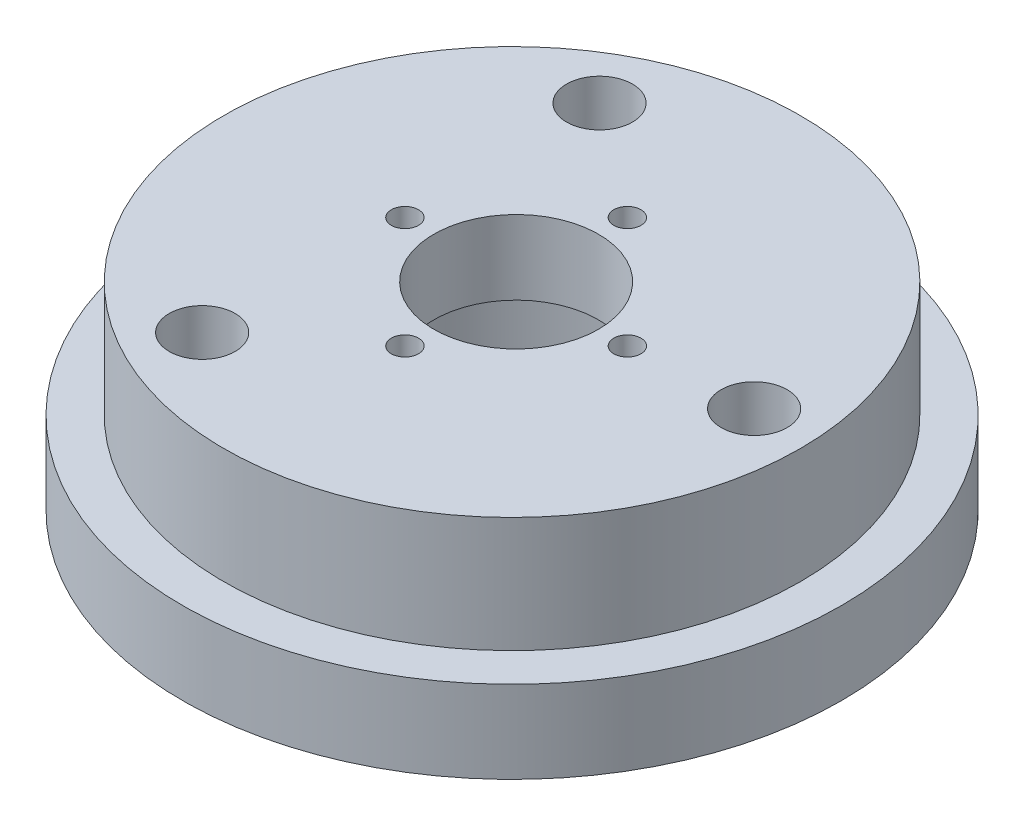
SolidWorks part; units mm, degrees
ref_plane "Front Plane" through (0, 0, 0) normal (0, 0, 1) x (1, 0, 0)
ref_plane "Top Plane" through (0, 0, 0) normal (0, 1, 0) x (1, 0, 0)
ref_plane "Right Plane" through (0, 0, 0) normal (1, 0, 0) x (0, 0, -1)
sketch "Sketch1" plane through (0, 0, 0) normal (0, 0, 1) x (1, 0, 0)
  line L5 (0, 12) -> (0, 0) construction
  line L7 (0, -1000) -> (0, 49000) construction
  line L8 (-40, 10) -> (-35, 10)
  line L9 (-35, 10) -> (-35, 24)
  line L10 (-40, 0) -> (-40, 10)
  line L11 (0, 0) -> (-40, 0)
  line L12 (-35, 24) -> (0, 24)
  line L13 (0, 0) -> (0, 24)
  dimension "D1" = 24
  dimension "D2" = 10
  dimension "D3" = 40
  dimension "D4" = 35
revolve "Revolve1" add sketch "Sketch1" angle 360 about L7
sketch "Sketch2" plane through (0, 0, 0) normal (0, -1, 0) x (1, 0, 0)
  line L0 (-999.7797, -0.2754) -> (49000.2203, -0.2754) construction
  line L1 (0.2203, -1000.2754) -> (0.2203, 48999.7246) construction
  line L2 (0.2203, -2000.2754) -> (0.2203, 97999.7246) construction
  line L3 (-1999.7797, -0.2754) -> (98000.2203, -0.2754) construction
  circle A0 centre (0.2203, -0.2754) radius 10
  circle A1 centre (-13.2797, -0.2754) radius 1.65
  circle A2 centre (13.7203, -0.2754) radius 1.65
  circle A3 centre (0.2203, -0.2754) radius 20
  circle A4 centre (0.2203, 13.2246) radius 1.65
  circle A5 centre (0.2203, -13.7754) radius 1.65
  dimension "D1" = 20
extrude "Cut-Extrude2" cut sketch "Sketch2" against normal through all both and the other way through all contours A0 | A2 | A5 | A1 | A4 region at (0.2203, 0, -0.2754) region at (-13.2797, 0, -0.2754) region at (13.7203, 0, -0.2754) region at (0.2203, 0, 13.2246) region at (0.2203, 0, -13.7754)
extrude "Cut-Extrude3" cut sketch "Sketch2<5>" against normal blind 15 contours A3 A5 A2 A0 A1 A4 region at (-19.214, 0, -0.2754)
sketch "Sketch2<5>" plane through (0, 0, 0) normal (0, -1, 0) x (1, 0, 0) same geometry as "Sketch2"
sketch "Sketch3" plane through (0, 24, 0) normal (0, 1, 0) x (1, 0, 0)
  line L0 (-51.5052, 0) -> (51.5052, 0) construction
  line L1 (0, 40.5863) -> (0, -40.5863) construction
  line L2 (-61.3064, 0) -> (61.3064, 0) construction
  line L3 (0, 58.4425) -> (0, -58.4425) construction
  circle A0 centre (28, 1.3821) radius 4
  circle A1 centre (-13.5, -24.11) radius 4
  circle A2 centre (-13.5, 24.1147) radius 4
  point P4 (0, 0)
  point P8 (0, 0)
  point P11 (0, 0)
  point P13 (0, 0)
  point P14 (-0.0801, 0.3773)
  point P21 (-0.0801, 0.3773)
  dimension "D1" = 8
  dimension "D2" = 28
  dimension "D3" = 13.5
  dimension "D4" = 24.11
  dimension "D5" = 24.1147
  dimension "D6" = 1.3821
extrude "Cut-Extrude4" cut sketch "Sketch3" against normal through all both and the other way through all
